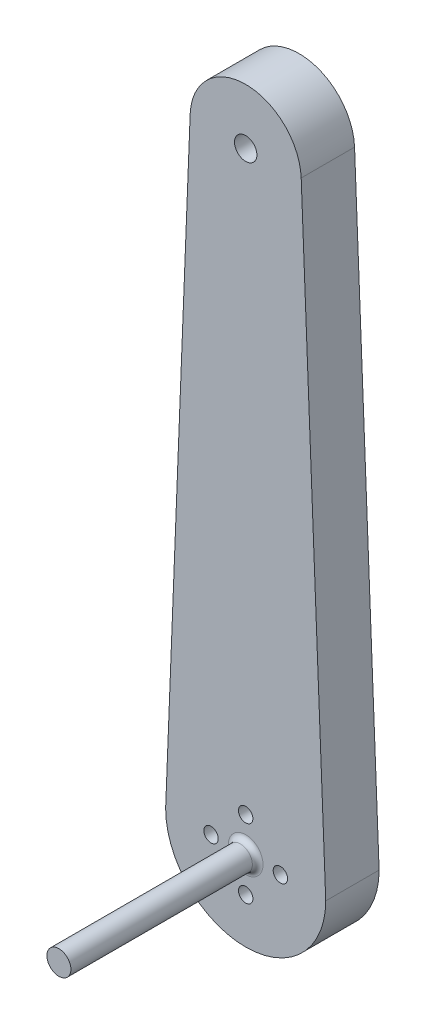
SolidWorks part; units mm, degrees
ref_plane "前视基准面" through (0, 0, 0) normal (0, 0, 1) x (1, 0, 0)
ref_plane "上视基准面" through (0, 0, 0) normal (0, 1, 0) x (1, 0, 0)
ref_plane "右视基准面" through (0, 0, 0) normal (1, 0, 0) x (0, 0, -1)
other "Configuration Table"
sketch "草图1" plane through (0, 0, 0) normal (0, 0, 1) x (1, 0, 0)
  line L1 (0, 0) -> (30, 0)
  line L2 (0, 0) -> (0, 140)
  line L3 (0, 140) -> (30, 140)
  line L4 (30, 0) -> (30, 140)
  dimension "D1" = 30
  dimension "D2" = 140
extrude "凸台-拉伸1" add sketch "草图1" along normal blind 10
fillet "圆角1" 2 edges at (0, 0, 5) (30, 0, 5) type full round first side face at (0, 70, 5) second side face at (30, 70, 5) middle face at (15, 0, 5)
sketch "草图2" plane through (0, 0, 10) normal (0, 0, 1) x (1, 0, 0)
  line L0 (0, 15) -> (5, 140)
  line L1 (30, 140) -> (0, 140) construction
  line L2 (30, 15) -> (25, 140)
  line L3 (0, 140) -> (0, 15) construction
  line L4 (30, 15) -> (30, 140) construction
  line L5 (0, 140) -> (0, 15)
  line L6 (30, 15) -> (30, 140)
  line L7 (30, 140) -> (25, 140)
  line L8 (5, 140) -> (0, 140)
  dimension "D1" = 20
  dimension "D2" = 5
extrude "切除-拉伸1" cut sketch "草图2" against normal blind 10
fillet "圆角2" 2 edges at (5, 140, 5) (25, 140, 5) type full round first side face at (2.5, 77.5, 5) second side face at (27.5, 77.5, 5) middle face at (15, 140, 5)
sketch "草图3" plane through (0, 0, 10) normal (0, 0, 1) x (1, 0, 0)
  circle A0 centre (15, 129.592) radius 2.1
  arc A1 (25.3997, 130.008) -> (4.6003, 130.008) centre (15, 129.592) ccw construction
  dimension "D1" = 4.2
extrude "切除-拉伸2" cut sketch "草图3" against normal through all
sketch "草图4" plane through (0, 0, 10) normal (0, 0, 1) x (1, 0, 0)
  line L0 (8.5, 15) -> (21.5, 15) construction
  line L1 (15, 21.5) -> (15, 8.5) construction
  circle A0 centre (15, 15) radius 6.5 construction
  circle A1 centre (15, 8.5) radius 1.35
  circle A2 centre (21.5, 15) radius 1.35
  circle A3 centre (15, 21.5) radius 1.35
  circle A4 centre (8.5, 15) radius 1.35
  dimension "D1" = 13
  dimension "D2" = 2.7
  dimension "D3" = 2.7
  dimension "D4" = 2.7
  dimension "D5" = 2.7
extrude "切除-拉伸3" cut sketch "草图4" against normal through all
sketch "草图5" plane through (0, 0, 10) normal (0, 0, 1) x (1, 0, 0)
  circle A1 centre (15, 15) radius 2.25
  dimension "D1" = 4.5
extrude "凸台-拉伸2" add sketch "草图5" along normal blind 35
fillet "圆角3" radius 1 1 edges at (12.75, 15, 10)
